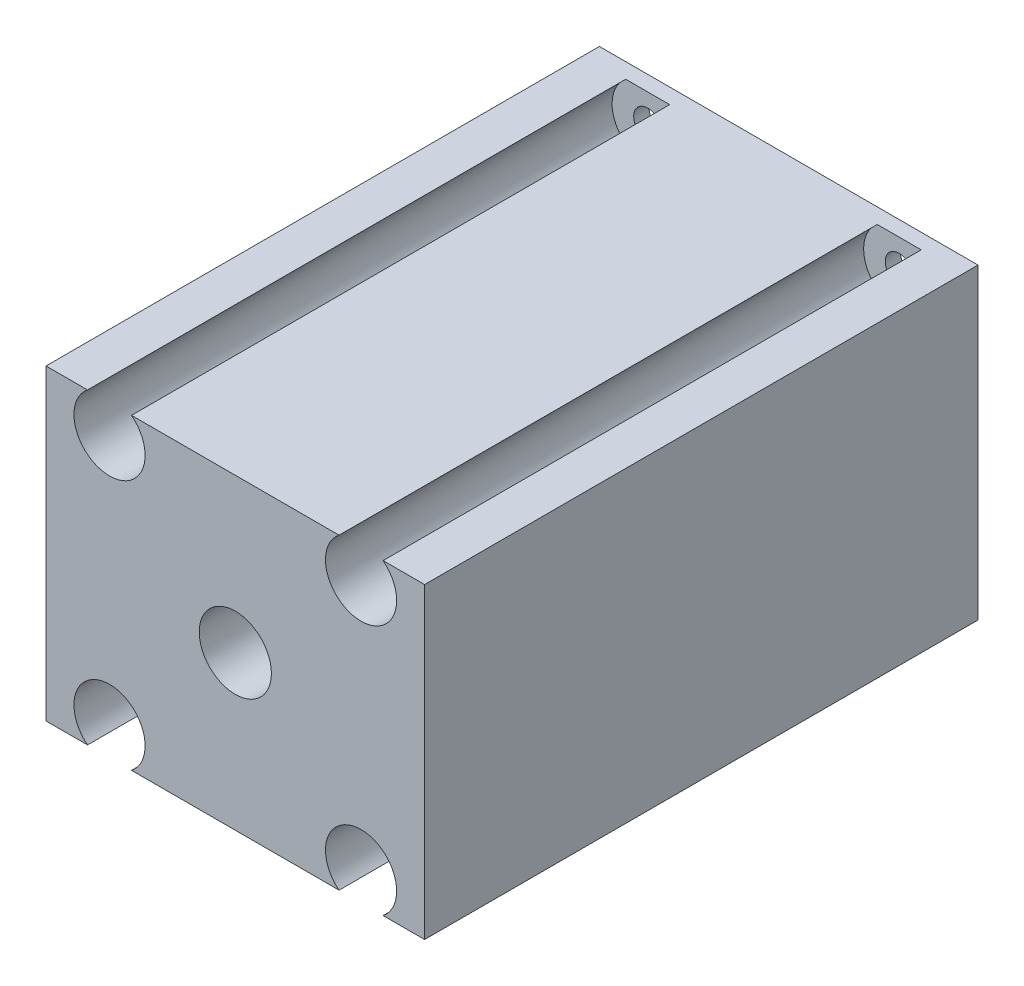
SolidWorks part; units mm, degrees
material "6061-T6 (SS)"
ref_plane "Front Plane" through (0, 0, 0) normal (0, 0, 1) x (1, 0, 0)
ref_plane "Top Plane" through (0, 0, 0) normal (0, 1, 0) x (1, 0, 0)
ref_plane "Right Plane" through (0, 0, 0) normal (1, 0, 0) x (0, 0, -1)
sketch "Sketch1" plane through (0, 0, 0) normal (0, 0, 1) x (1, 0, 0)
  line L1 (-37.25, -30.25) -> (37.25, -30.25)
  line L2 (-37.25, -30.25) -> (-37.25, 30.25)
  line L3 (-37.25, 30.25) -> (37.25, 30.25)
  line L4 (37.25, -30.25) -> (37.25, 30.25)
  circle A0 centre (0, 0) radius 7.1
extrude "Conservative_Manufacturer_Case_Envelope" add sketch "Sketch1" along normal blind 108.9
sketch "Sketch2" plane through (0, 0, 0) normal (0, 0, 1) x (1, 0, 0)
  circle A0 centre (0, 0) radius 25
  circle A1 centre (0, 0) radius 7.1
extrude "D50_Pilot_Envelope" add sketch "Sketch2" along normal blind 2 from offset 2 offset against normal yes
sketch "Sketch3" plane through (0, 0, 108.9) normal (0, 0, 1) x (1, 0, 0)
  circle A0 centre (-24.7487, -24.7487) radius 2.75
  circle A1 centre (-24.7487, 24.7487) radius 2.75
  circle A2 centre (24.7487, -24.7487) radius 2.75
  circle A3 centre (24.7487, 24.7487) radius 2.75
extrude "Bench_PCD70_Flange_Holes_4x_D5p5" cut sketch "Sketch3" against normal blind 109.5
sketch "Sketch4" plane through (0, 0, 108.9) normal (0, 0, 1) x (1, 0, 0)
  circle A0 centre (-24.7487, -24.7487) radius 7
  circle A1 centre (-24.7487, 24.7487) radius 7
  circle A2 centre (24.7487, -24.7487) radius 7
  circle A3 centre (24.7487, 24.7487) radius 7
extrude "Bench_PCD70_Flange_Back_Relief_4x_D14" cut sketch "Sketch4" against normal blind 105.9
